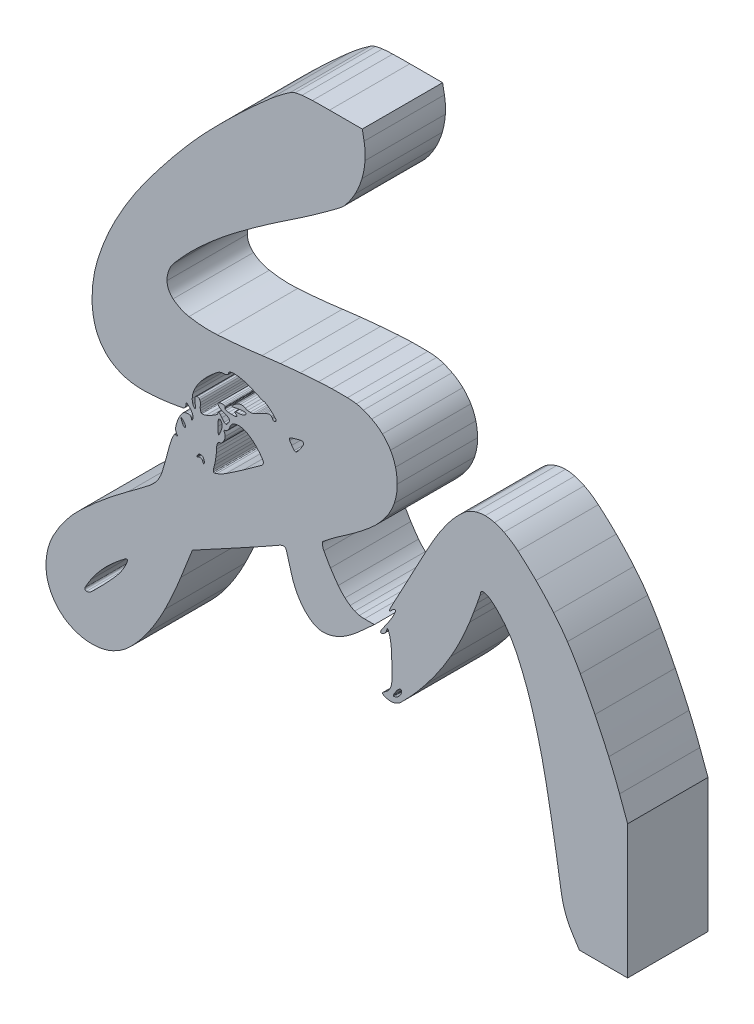
SolidWorks part; units mm, degrees
ref_plane "Front Plane" through (0, 0, 0) normal (0, 0, 1) x (1, 0, 0)
ref_plane "Top Plane" through (0, 0, 0) normal (0, 1, 0) x (1, 0, 0)
ref_plane "Right Plane" through (0, 0, 0) normal (1, 0, 0) x (0, 0, -1)
sketch "Sketch2" plane through (0, 0, 0) normal (0, 0, 1) x (1, 0, 0)
  line L0 (58.1325, 46.1079) -> (62.4633, 57.0965)
  line L1 (62.4633, 57.0965) -> (75.9817, 64.4271)
  line L2 (75.9817, 64.4271) -> (81.4318, 67.3962)
  line L3 (81.4318, 67.3962) -> (86.629, 70.2555)
  line L4 (86.629, 70.2555) -> (91.0276, 72.6996)
  line L5 (97.713, 74.0169) -> (98.2521, 72.1906)
  line L6 (98.2521, 72.1906) -> (98.8813, 70.0175)
  line L7 (98.8813, 70.0175) -> (99.54, 67.697)
  line L8 (125.4581, 62.5021) -> (130.4161, 67)
  line L9 (130.4161, 67) -> (126.7429, 67)
  line L10 (126.5831, 221.4085) -> (125.9094, 225)
  line L11 (125.9094, 225) -> (113.6772, 225)
  line L12 (84.7821, 120.3404) -> (86.2428, 119.6975)
  line L13 (87.5547, 119.1396) -> (88.6641, 118.6831)
  line L14 (89.9287, 114.9639) -> (89.0442, 114.5211)
  line L15 (89.0442, 114.5211) -> (87.9723, 113.9827)
  line L16 (87.9723, 113.9827) -> (86.8914, 113.4387)
  line L17 (86.8914, 113.4387) -> (85.977, 112.9771)
  line L18 (145.0185, 91.5) -> (143.1759, 88.0347)
  line L19 (143.1759, 88.0347) -> (141.1487, 84.2344)
  line L20 (141.1487, 84.2344) -> (139.2415, 80.6687)
  line L21 (139.2415, 80.6687) -> (137.8075, 78)
  line L22 (204.0561, 4.5726) -> (206.956, 0)
  line L23 (206.956, 0) -> (215.978, 0)
  line L24 (215.978, 0) -> (225, 0)
  line L25 (225, 0) -> (225, 24.9318)
  line L26 (225, 24.9318) -> (225, 49.8636)
  line L27 (225, 49.8636) -> (221.9881, 58.0323)
  arc A0 (98.9725, 223.3296) -> (91.3359, 217.4477) centre (142.3937, 159.0566) ccw
  arc A1 (91.3359, 217.4477) -> (80.6992, 207.7701) centre (331.2459, -56.9208) ccw
  arc A2 (80.6992, 207.7701) -> (69.7304, 196.9582) centre (342.3048, -68.6048) ccw
  arc A3 (69.7304, 196.9582) -> (60.5919, 187) centre (231.7944, 39.0629) ccw
  arc A4 (60.5919, 187) -> (44.8059, 167.1501) centre (295.9522, -16.3757) ccw
  arc A5 (44.8059, 167.1501) -> (33.7717, 149.478) centre (160.2656, 82.7777) ccw
  arc A6 (33.7717, 149.478) -> (27.1754, 133.6598) centre (117.9519, 105.0897) ccw
  arc A7 (27.1754, 133.6598) -> (25, 119.5018) centre (72.1599, 119.5018) ccw
  arc A8 (25, 119.5018) -> (25.9759, 112.0838) centre (53.6811, 119.5018) ccw
  arc A9 (25.9759, 112.0838) -> (28.8483, 106.1709) centre (42.735, 116.571) ccw
  arc A10 (28.8483, 106.1709) -> (33.4937, 102.0925) centre (40.8582, 115.1654) ccw
  arc A11 (33.4937, 102.0925) -> (39.6189, 99.9819) centre (42.3159, 117.7531) ccw
  arc A12 (39.6189, 99.9819) -> (45.2486, 99.6601) centre (44.1501, 129.8391) ccw
  arc A13 (45.2486, 99.6601) -> (52.2921, 100.2566) centre (42.5757, 173.0935) ccw
  arc A14 (52.2921, 100.2566) -> (58.8811, 101.3412) centre (37.8213, 208.7339) ccw
  arc A15 (58.8811, 101.3412) -> (60, 102.7008) centre (58.6145, 102.7008) ccw
  arc A16 (60.0652, 103.3967) -> (60, 102.7008) centre (63.7457, 102.7008) ccw
  arc A17 (60.2979, 103.573) -> (60.0652, 103.3967) centre (60.279, 103.3563) ccw
  arc A18 (60.7041, 103.3959) -> (60.2979, 103.573) centre (60.2373, 102.8798) ccw
  arc A19 (61.5804, 102.5625) -> (60.7041, 103.3959) centre (44.5195, 85.5017) ccw
  arc A20 (62.1476, 101.8659) -> (61.5804, 102.5625) centre (58.4608, 99.4429) ccw
  arc A21 (62.5492, 101.0818) -> (62.1476, 101.8659) centre (58.7353, 99.6233) ccw
  arc A22 (62.7365, 100.3314) -> (62.5492, 101.0818) centre (59.5482, 99.9342) ccw
  arc A23 (62.6593, 99.7411) -> (62.7365, 100.3314) centre (61.5607, 100.1849) ccw
  arc A24 (62.4218, 99.2055) -> (62.6593, 99.7411) centre (54.5524, 103.0164) ccw
  arc A25 (62.2615, 99.0881) -> (62.4218, 99.2055) centre (62.2309, 99.2979) ccw
  arc A26 (62.1376, 99.1775) -> (62.2615, 99.0881) centre (62.2457, 99.1967) ccw
  arc A27 (62.0789, 99.6564) -> (62.1376, 99.1775) centre (66.5589, 99.9622) ccw
  arc A28 (62.0789, 99.6564) -> (61.8949, 100.06) centre (61.4503, 99.6135) ccw
  arc A29 (61.8949, 100.06) -> (61.4536, 100.3275) centre (61.1237, 99.2854) ccw
  arc A30 (61.4536, 100.3275) -> (60.8046, 100.4144) centre (60.8806, 98.5175) ccw
  arc A31 (60.8046, 100.4144) -> (60.0427, 100.3009) centre (60.9479, 96.8397) ccw
  arc A32 (60.0427, 100.3009) -> (58.4846, 99.2035) centre (60.731, 97.6689) ccw
  arc A33 (58.4846, 99.2035) -> (57.0681, 96.5746) centre (70.239, 91.1736) ccw
  arc A34 (57.0681, 96.5746) -> (56.2329, 93.7146) centre (70.212, 91.1847) ccw
  arc A35 (56.2329, 93.7146) -> (56.5834, 91.865) centre (58.8188, 93.2466) ccw
  arc A36 (56.8204, 91.4259) -> (56.5834, 91.865) centre (52.9657, 89.6292) ccw
  arc A37 (56.815, 91.2024) -> (56.8204, 91.4259) centre (56.5923, 91.3196) ccw
  arc A38 (56.6544, 91.1412) -> (56.815, 91.2024) centre (56.7, 91.2629) ccw
  arc A39 (56.2953, 91.3175) -> (56.6544, 91.1412) centre (57.3783, 93.0697) ccw
  arc A40 (56.2953, 91.3175) -> (55.7849, 91.1994) centre (56.0997, 91.0009) ccw
  arc A41 (55.7849, 91.1994) -> (55.0801, 89.8876) centre (64.8532, 85.482) ccw
  arc A42 (55.0801, 89.8876) -> (54.3124, 87.8818) centre (71.9717, 82.273) ccw
  arc A43 (54.3124, 87.8818) -> (53.5476, 85.222) centre (102.2212, 72.6655) ccw
  arc A44 (51.1765, 76.7767) -> (53.5476, 85.222) centre (-146.3837, 136.7991) ccw
  arc A45 (49.3624, 73.0806) -> (51.1765, 76.7767) centre (38.9119, 80.5029) ccw
  arc A46 (46.4159, 70.003) -> (49.3624, 73.0806) centre (37.4294, 81.5559) ccw
  arc A47 (38.5117, 64.0517) -> (46.4159, 70.003) centre (-146.6931, 318.2601) ccw
  arc A48 (38.5117, 64.0517) -> (20.7518, 49.2864) centre (144.9076, -81.9855) ccw
  arc A49 (20.7518, 49.2864) -> (10.5895, 35.9714) centre (56.576, 11.4089) ccw
  arc A50 (10.5895, 35.9714) -> (7.8151, 24.1947) centre (31.4083, 24.8516) ccw
  arc A51 (7.8151, 24.1947) -> (11.7296, 13.9095) centre (24.5051, 24.6594) ccw
  arc A52 (11.7296, 13.9095) -> (16.0112, 10.3476) centre (23.8048, 24.0701) ccw
  arc A53 (16.0112, 10.3476) -> (21.4133, 8.3391) centre (24.9134, 26.022) ccw
  arc A54 (21.4133, 8.3391) -> (27.2661, 8.1176) centre (25.0366, 26.6446) ccw
  arc A55 (27.2661, 8.1176) -> (32.8489, 9.7292) centre (25.1044, 26.0814) ccw
  arc A56 (32.8489, 9.7292) -> (39.3723, 14.3529) centre (22.9802, 30.5665) ccw
  arc A57 (39.3723, 14.3529) -> (45.8866, 22.1873) centre (-2.6611, 55.9285) ccw
  arc A58 (45.8866, 22.1873) -> (52.2059, 32.8307) centre (-25.1859, 71.5834) ccw
  arc A59 (52.2059, 32.8307) -> (58.1325, 46.1079) centre (-94.2409, 106.1615) ccw
  arc A60 (91.0276, 72.6996) -> (93.2447, 73.9745) centre (41.8134, 160.8536) ccw
  arc A61 (95.1566, 75.0372) -> (93.2447, 73.9745) centre (113.7591, 39.321) ccw
  arc A62 (96.3011, 75.445) -> (95.1566, 75.0372) centre (97.1978, 71.1182) ccw
  arc A63 (97.0065, 75.3524) -> (96.3011, 75.445) centre (96.5207, 74.3851) ccw
  arc A64 (97.4483, 74.8456) -> (97.0065, 75.3524) centre (96.6081, 74.559) ccw
  arc A65 (97.713, 74.0169) -> (97.4483, 74.8456) centre (76.4663, 67.6891) ccw
  arc A66 (99.54, 67.697) -> (101.5193, 62.7234) centre (124.2446, 74.6478) ccw
  arc A67 (101.5193, 62.7234) -> (104.3859, 58.6357) centre (118.7877, 71.7844) ccw
  arc A68 (104.3859, 58.6357) -> (107.7326, 55.9243) centre (115.0327, 68.3561) ccw
  arc A69 (107.7326, 55.9243) -> (111.1322, 55) centre (111.1322, 61.7138) ccw
  arc A70 (111.1322, 55) -> (114.3727, 55.4474) centre (111.1322, 66.9579) ccw
  arc A71 (114.3727, 55.4474) -> (117.7122, 56.7752) centre (109.6818, 72.1098) ccw
  arc A72 (117.7122, 56.7752) -> (121.3361, 59.0778) centre (105.7891, 79.5433) ccw
  arc A73 (121.3361, 59.0778) -> (125.4581, 62.5021) centre (84.1117, 108.0785) ccw
  arc A74 (124.8181, 67.1788) -> (126.7429, 67) centre (126.7429, 77.4472) ccw
  arc A75 (123.0863, 67.71) -> (124.8181, 67.1788) centre (126.3071, 75.1224) ccw
  arc A76 (121.3674, 68.6716) -> (123.0863, 67.71) centre (127.0128, 76.7464) ccw
  arc A77 (119.4706, 70.16) -> (121.3674, 68.6716) centre (133.8896, 86.5824) ccw
  arc A78 (116.9314, 72.9113) -> (119.4706, 70.16) centre (131.2624, 83.5902) ccw
  arc A79 (114.0429, 77.1489) -> (116.9314, 72.9113) centre (165.7714, 109.3048) ccw
  arc A80 (111.5801, 81.443) -> (114.0429, 77.1489) centre (173.3859, 114.0381) ccw
  arc A81 (111, 83.7864) -> (111.5801, 81.443) centre (116.0236, 83.7864) ccw
  arc A82 (111.2406, 84.2918) -> (111, 83.7864) centre (111.651, 83.7864) ccw
  arc A83 (113.4645, 86.0629) -> (111.2406, 84.2918) centre (205.3287, -31.5713) ccw
  arc A84 (116.1742, 88.0924) -> (113.4645, 86.0629) centre (165.1493, 19.8795) ccw
  arc A85 (119.3898, 90.3383) -> (116.1742, 88.0924) centre (204.134, -34.4186) ccw
  arc A86 (119.3898, 90.3383) -> (128.5689, 97.2876) centre (56.3578, 183.1316) ccw
  arc A87 (128.5689, 97.2876) -> (134.5246, 103.6168) centre (104.4908, 125.9114) ccw
  arc A88 (134.5246, 103.6168) -> (137.8519, 109.922) centre (115.7444, 117.5577) ccw
  arc A89 (137.8519, 109.922) -> (138.9718, 116.7179) centre (118.5246, 116.5974) ccw
  arc A90 (138.9718, 116.7179) -> (138.3179, 121.8604) centre (117.4279, 116.591) ccw
  arc A91 (138.3179, 121.8604) -> (136.4575, 126.4089) centre (121.3825, 117.5886) ccw
  arc A92 (136.4575, 126.4089) -> (133.4568, 130.1619) centre (122.113, 118.016) ccw
  arc A93 (133.4568, 130.1619) -> (129.4599, 132.9749) centre (121.3319, 117.1797) ccw
  arc A94 (129.4599, 132.9749) -> (126.3756, 134.3466) centre (115.849, 106.5245) ccw
  arc A95 (126.3756, 134.3466) -> (123.7052, 135.055) centre (121.5939, 121.7084) ccw
  arc A96 (123.7052, 135.055) -> (120.3559, 135.3426) centre (120.0157, 111.7319) ccw
  arc A97 (120.3559, 135.3426) -> (114.5264, 135.3373) centre (117.6143, -54.9073) ccw
  arc A98 (114.5264, 135.3373) -> (109.5747, 135.1292) centre (116.0872, 39.181) ccw
  arc A99 (109.5747, 135.1292) -> (102.7453, 134.5966) centre (132.6587, -204.9678) ccw
  arc A100 (102.7453, 134.5966) -> (95.3604, 133.872) centre (135.5077, -237.305) ccw
  arc A101 (95.3604, 133.872) -> (88.5, 133.0445) centre (125.5632, -145.3621) ccw
  arc A102 (71.7969, 131.3896) -> (88.5, 133.0445) centre (55.5242, 380.749) ccw
  arc A103 (61.2042, 132.0029) -> (71.7969, 131.3896) centre (68.9811, 174.5386) ccw
  arc A104 (55.2638, 134.7535) -> (61.2042, 132.0029) centre (63.5578, 144.8757) ccw
  arc A105 (53, 139.5351) -> (55.2638, 134.7535) centre (59.1818, 139.5351) ccw
  arc A106 (55.4713, 146.3194) -> (53, 139.5351) centre (63.548, 139.5351) ccw
  arc A107 (65.0484, 156.4067) -> (55.4713, 146.3194) centre (143.0943, 72.7179) ccw
  arc A108 (79.262, 168.2983) -> (65.0484, 156.4067) centre (182.4811, 30.4836) ccw
  arc A109 (98.0934, 181.588) -> (79.262, 168.2983) centre (323.5476, -157.8641) ccw
  arc A110 (98.0934, 181.588) -> (105.4767, 186.5917) centre (-166.3038, 579.6742) ccw
  arc A111 (105.4767, 186.5917) -> (112.1241, 191.3089) centre (-84.2329, 460.9727) ccw
  arc A112 (112.1241, 191.3089) -> (117.5951, 195.37) centre (-106.3283, 491.3164) ccw
  arc A113 (117.5951, 195.37) -> (119.4848, 197.1643) centre (110.5471, 204.6849) ccw
  arc A114 (119.4848, 197.1643) -> (123.2583, 202.7225) centre (94.5057, 218.1829) ccw
  arc A115 (123.2583, 202.7225) -> (125.7969, 208.9144) centre (94.942, 217.9483) ccw
  arc A116 (125.7969, 208.9144) -> (126.9386, 215.2943) centre (96.8791, 217.3811) ccw
  arc A117 (126.9386, 215.2943) -> (126.5831, 221.4085) centre (102.8908, 216.9638) ccw
  arc A118 (113.6772, 225) -> (107.2821, 224.9286) centre (113.677, -61.3918) ccw
  arc A119 (107.2821, 224.9286) -> (103.4004, 224.6653) centre (108.2393, 182.0677) ccw
  arc A120 (103.4004, 224.6653) -> (100.8077, 224.1698) centre (105.3697, 207.3295) ccw
  arc A121 (100.8077, 224.1698) -> (98.9725, 223.3296) centre (102.4162, 218.2323) ccw
  arc A122 (86.2428, 119.6975) -> (87.5547, 119.1396) centre (125.0172, 209.0572) ccw
  arc A123 (88.6641, 118.6831) -> (89, 118.5831) centre (89.3488, 120.368) ccw
  arc A124 (90.4252, 117.9747) -> (89, 118.5831) centre (88.2888, 114.9434) ccw
  arc A125 (92.175, 116.5423) -> (90.4252, 117.9747) centre (81.3766, 105.1359) ccw
  arc A126 (93.6023, 115.0051) -> (92.175, 116.5423) centre (80.9796, 104.7166) ccw
  arc A127 (93.5528, 114.273) -> (93.6023, 115.0051) centre (93.1856, 114.6656) ccw
  arc A128 (93.2039, 114.0742) -> (93.5528, 114.273) centre (92.9611, 114.9056) ccw
  arc A129 (92.8414, 114.0837) -> (93.2039, 114.0742) centre (93.0374, 114.6443) ccw
  arc A130 (92.5203, 114.3089) -> (92.8414, 114.0837) centre (93.0795, 114.7645) ccw
  arc A131 (92.2918, 114.7139) -> (92.5203, 114.3089) centre (93.5856, 115.1769) ccw
  arc A132 (92.2918, 114.7139) -> (91.9742, 115.1974) centre (91.1349, 114.2999) ccw
  arc A133 (91.9742, 115.1974) -> (91.5037, 115.4124) centre (91.418, 114.6027) ccw
  arc A134 (91.5037, 115.4124) -> (90.8388, 115.3404) centre (91.3374, 113.8408) ccw
  arc A135 (90.8388, 115.3404) -> (89.9287, 114.9639) centre (93.0221, 108.7745) ccw
  arc A136 (85.01, 112.6087) -> (85.977, 112.9771) centre (83.729, 117.4232) ccw
  arc A137 (84.028, 112.4682) -> (85.01, 112.6087) centre (83.9262, 116.6822) ccw
  arc A138 (83.0801, 112.5626) -> (84.028, 112.4682) centre (83.9345, 116.3354) ccw
  arc A139 (82.2128, 112.8861) -> (83.0801, 112.5626) centre (83.8434, 115.9331) ccw
  arc A140 (82.2128, 112.8861) -> (81.3093, 113.2107) centre (80.6611, 109.9869) ccw
  arc A141 (81.3093, 113.2107) -> (80.413, 113.2282) centre (80.8127, 110.7407) ccw
  arc A142 (80.413, 113.2282) -> (79.4853, 112.923) centre (80.9038, 110.1738) ccw
  arc A143 (79.4853, 112.923) -> (78.4858, 112.2873) centre (82.5008, 107.0786) ccw
  arc A144 (78.4858, 112.2873) -> (77.2596, 111.3101) centre (108.0536, 73.9287) ccw
  arc A145 (77.2596, 111.3101) -> (77.2689, 111.0675) centre (77.3566, 111.1923) ccw
  arc A146 (77.2689, 111.0675) -> (77.6467, 110.9822) centre (77.5614, 111.4835) ccw
  arc A147 (77.6467, 110.9822) -> (79.7997, 111.3632) centre (49.9752, 273.588) ccw
  arc A148 (81.1568, 111.5606) -> (79.7997, 111.3632) centre (83.1181, 93.3134) ccw
  arc A149 (82.0584, 111.5459) -> (81.1568, 111.5606) centre (81.5483, 107.9178) ccw
  arc A150 (82.4598, 111.332) -> (82.0584, 111.5459) centre (81.966, 110.8891) ccw
  arc A151 (82.4907, 110.9849) -> (82.4598, 111.332) centre (82.2433, 111.1378) ccw
  arc A152 (82.1029, 110.6056) -> (82.4907, 110.9849) centre (81.5307, 111.5783) ccw
  arc A153 (81.4172, 110.2848) -> (82.1029, 110.6056) centre (80.065, 114.0695) ccw
  arc A154 (80.5743, 110.0634) -> (81.4172, 110.2848) centre (79.7146, 115.0504) ccw
  arc A155 (79.691, 109.9847) -> (80.5743, 110.0634) centre (79.6531, 115.4071) ccw
  arc A156 (79.691, 109.9847) -> (78.7122, 109.943) centre (79.7871, 96.2308) ccw
  arc A157 (78.7122, 109.943) -> (78.3331, 109.7772) centre (78.7615, 109.3137) ccw
  arc A158 (78.3331, 109.7772) -> (78.3273, 109.5241) centre (78.4527, 109.6478) ccw
  arc A159 (78.3273, 109.5241) -> (78.7893, 109.1514) centre (80.1947, 111.3664) ccw
  arc A160 (79.0766, 108.8137) -> (78.7893, 109.1514) centre (78.388, 108.5188) ccw
  arc A161 (78.9753, 108.544) -> (79.0766, 108.8137) centre (78.8852, 108.7317) ccw
  arc A162 (78.3339, 108.3753) -> (78.9753, 108.544) centre (78.216, 110.1274) ccw
  arc A163 (77.0833, 108.3333) -> (78.3339, 108.3753) centre (77.0833, 126.9683) ccw
  arc A164 (75.9699, 108.3923) -> (77.0833, 108.3333) centre (77.0833, 118.8687) ccw
  arc A165 (75.1192, 108.5781) -> (75.9699, 108.3923) centre (76.3925, 112.368) ccw
  arc A166 (74.6495, 108.8501) -> (75.1192, 108.5781) centre (75.5525, 109.8678) ccw
  arc A167 (74.603, 109.1667) -> (74.6495, 108.8501) centre (74.8144, 109.036) ccw
  arc A168 (74.603, 109.1667) -> (74.667, 109.4821) centre (74.2074, 109.4112) ccw
  arc A169 (74.667, 109.4821) -> (74.5088, 109.7552) centre (74.2379, 109.4159) ccw
  arc A170 (74.5088, 109.7552) -> (74.1197, 109.94) centre (73.92, 109.0176) ccw
  arc A171 (74.1197, 109.94) -> (73.559, 110) centre (73.559, 107.3498) ccw
  arc A172 (73.559, 110) -> (72.3614, 109.7153) centre (73.559, 107.3387) ccw
  arc A173 (72.3614, 109.7153) -> (72.0749, 109.0139) centre (72.621, 109.2001) ccw
  arc A174 (72.0749, 109.0139) -> (72.8162, 108.0965) centre (73.6978, 109.5671) ccw
  arc A175 (72.8162, 108.0965) -> (74.468, 107.3333) centre (77.1882, 115.3895) ccw
  arc A176 (75.6567, 106.8492) -> (74.468, 107.3333) centre (71.1061, 97.3771) ccw
  arc A177 (76.2077, 106.3595) -> (75.6567, 106.8492) centre (75.0765, 105.6415) ccw
  arc A178 (76.2969, 105.7728) -> (76.2077, 106.3595) centre (75.5861, 105.9649) ccw
  arc A179 (75.949, 105) -> (76.2969, 105.7728) centre (73.7124, 106.4716) ccw
  arc A180 (75.3545, 104.2593) -> (75.949, 105) centre (71.7378, 107.7708) ccw
  arc A181 (74.8752, 104.1049) -> (75.3545, 104.2593) centre (74.9696, 104.6331) ccw
  arc A182 (74.3444, 104.4) -> (74.8752, 104.1049) centre (75.0398, 105.026) ccw
  arc A183 (73.481, 105.4411) -> (74.3444, 104.4) centre (86.7357, 115.5539) ccw
  arc A184 (73.481, 105.4411) -> (72.9106, 106.1189) centre (66.1124, 99.8192) ccw
  arc A185 (72.9106, 106.1189) -> (72.435, 106.5093) centre (71.2476, 104.5778) ccw
  arc A186 (72.435, 106.5093) -> (72.1445, 106.5467) centre (72.2483, 106.2056) ccw
  arc A187 (72.1445, 106.5467) -> (72, 106.3516) centre (72.2039, 106.3516) ccw
  arc A188 (71.5632, 105.5006) -> (72, 106.3516) centre (70.9525, 106.3516) ccw
  arc A189 (69.6838, 104.3028) -> (71.5632, 105.5006) centre (59.7557, 121.9541) ccw
  arc A190 (67.5963, 103.3011) -> (69.6838, 104.3028) centre (60.94, 119.8487) ccw
  arc A191 (66.041, 103) -> (67.5963, 103.3011) centre (66.041, 107.1674) ccw
  arc A192 (65.7288, 103.1717) -> (66.041, 103) centre (66.041, 103.3697) ccw
  arc A193 (65.5054, 103.6854) -> (65.7288, 103.1717) centre (67.2612, 104.1435) ccw
  arc A194 (65.397, 104.4394) -> (65.5054, 103.6854) centre (68.792, 104.5429) ccw
  arc A195 (65.4322, 105.3333) -> (65.397, 104.4394) centre (71.7985, 104.6345) ccw
  arc A196 (65.4322, 105.3333) -> (65.4467, 106.2855) centre (60.3974, 105.886) ccw
  arc A197 (65.4467, 106.2855) -> (65.2528, 107.0272) centre (63.2741, 106.1136) ccw
  arc A198 (65.2528, 107.0272) -> (64.8745, 107.494) centre (64.1434, 106.515) ccw
  arc A199 (64.8745, 107.494) -> (64.3549, 107.6667) centre (64.3549, 106.7981) ccw
  arc A200 (64.3549, 107.6667) -> (63.8193, 107.4943) centre (64.3549, 106.7483) ccw
  arc A201 (63.8193, 107.4943) -> (63.4754, 107.0397) centre (64.3807, 106.7124) ccw
  arc A202 (63.4754, 107.0397) -> (63.354, 106.2766) centre (65.4077, 106.341) ccw
  arc A203 (63.354, 106.2766) -> (63.4667, 105.2106) centre (70.5968, 106.5036) ccw
  arc A204 (63.5939, 104.3092) -> (63.4667, 105.2106) centre (52.0312, 103.137) ccw
  arc A205 (63.5898, 103.6675) -> (63.5939, 104.3092) centre (60.6166, 104.0074) ccw
  arc A206 (63.4597, 103.4043) -> (63.5898, 103.6675) centre (63.1591, 103.7167) ccw
  arc A207 (63.2604, 103.4062) -> (63.4597, 103.4043) centre (63.361, 103.5069) ccw
  arc A208 (62.5878, 104.5678) -> (63.2604, 103.4062) centre (65.1027, 105.2485) ccw
  arc A209 (62.4059, 106.1797) -> (62.5878, 104.5678) centre (67.7601, 105.9677) ccw
  arc A210 (62.7227, 108.0691) -> (62.4059, 106.1797) centre (69.9896, 105.8795) ccw
  arc A211 (63.5232, 110.0449) -> (62.7227, 108.0691) centre (73.7963, 104.7325) ccw
  arc A212 (65.6306, 113.2542) -> (63.5232, 110.0449) centre (79.9842, 101.5326) ccw
  arc A213 (68.727, 116.5951) -> (65.6306, 113.2542) centre (93.8108, 90.2414) ccw
  arc A214 (71.9174, 119.3064) -> (68.727, 116.5951) centre (94.3695, 89.6543) ccw
  arc A215 (73.9823, 120) -> (71.9174, 119.3064) centre (73.9823, 116.5793) ccw
  arc A216 (73.9823, 120) -> (74.7545, 120.0737) centre (73.9823, 124.0841) ccw
  arc A217 (74.7545, 120.0737) -> (75.4073, 120.2938) centre (74.2705, 122.5874) ccw
  arc A218 (75.4073, 120.2938) -> (75.8473, 120.6181) centre (74.7104, 121.6999) ccw
  arc A219 (75.8473, 120.6181) -> (76, 121) centre (75.446, 121) ccw
  arc A220 (76.6849, 121.823) -> (76, 121) centre (76.837, 121) ccw
  arc A221 (78.839, 121.9392) -> (76.6849, 121.823) centre (78.2104, 113.5691) ccw
  arc A222 (81.7444, 121.4325) -> (78.839, 121.9392) centre (77.707, 106.8668) ccw
  arc A223 (84.7821, 120.3404) -> (81.7444, 121.4325) centre (75.9693, 100.5978) ccw
  arc A224 (103.869, 111.8438) -> (103.9682, 112.25) centre (102.9014, 112.2952) ccw
  arc A225 (103.5145, 111.1501) -> (103.869, 111.8438) centre (94.0543, 116.4231) ccw
  arc A226 (103.0326, 110.357) -> (103.5145, 111.1501) centre (92.6957, 117.1803) ccw
  arc A227 (102.4682, 109.5589) -> (103.0326, 110.357) centre (90.3071, 118.757) ccw
  arc A228 (101.4893, 108.3411) -> (102.4682, 109.5589) centre (81.3666, 125.5193) ccw
  arc A229 (101.0049, 108.1177) -> (101.4893, 108.3411) centre (101.0049, 108.7545) ccw
  arc A230 (100.5243, 108.3426) -> (101.0049, 108.1177) centre (101.0049, 108.7438) ccw
  arc A231 (99.5701, 109.5589) -> (100.5243, 108.3426) centre (120.0849, 124.6702) ccw
  arc A232 (98.8012, 110.7091) -> (99.5701, 109.5589) centre (111.7916, 118.5613) ccw
  arc A233 (98.7245, 111.2911) -> (98.8012, 110.7091) centre (99.4275, 111.0876) ccw
  arc A234 (99.1016, 111.7144) -> (98.7245, 111.2911) centre (99.3558, 111.1084) ccw
  arc A235 (100.3201, 112.1503) -> (99.1016, 111.7144) centre (103.7706, 100.5845) ccw
  arc A236 (102.3571, 112.7254) -> (100.3201, 112.1503) centre (120.8162, 43.4481) ccw
  arc A237 (103.3261, 112.8658) -> (102.3571, 112.7254) centre (103.4411, 108.6573) ccw
  arc A238 (103.7884, 112.6903) -> (103.3261, 112.8658) centre (103.3438, 112.2159) ccw
  arc A239 (103.9682, 112.25) -> (103.7884, 112.6903) centre (103.3985, 112.2742) ccw
  arc A240 (87.0997, 101.659) -> (85.9231, 102.9231) centre (68.8756, 85.8755) ccw
  arc A241 (88.0899, 100.4054) -> (87.0997, 101.659) centre (73.7399, 90.0884) ccw
  arc A242 (88.8105, 99.3062) -> (88.0899, 100.4054) centre (75.6842, 91.4863) ccw
  arc A243 (88.9786, 98.6731) -> (88.8105, 99.3062) centre (87.7843, 98.6948) ccw
  arc A244 (88.3498, 97.4668) -> (88.9786, 98.6731) centre (87.454, 98.7008) ccw
  arc A245 (81.5534, 92.6033) -> (88.3498, 97.4668) centre (-275.5146, 598.7614) ccw
  arc A246 (75.0593, 88.1799) -> (81.5534, 92.6033) centre (-56.414, 288.178) ccw
  arc A247 (71.5584, 86.384) -> (75.0593, 88.1799) centre (64.9934, 103.4921) ccw
  arc A248 (70.7131, 86.1697) -> (71.5584, 86.384) centre (70.2327, 89.8388) ccw
  arc A249 (70.3429, 86.3879) -> (70.7131, 86.1697) centre (70.6677, 86.516) ccw
  arc A250 (70.2899, 87.0305) -> (70.3429, 86.3879) centre (71.3803, 86.797) ccw
  arc A251 (70.6753, 88.6235) -> (70.2899, 87.0305) centre (100.6544, 80.5267) ccw
  arc A252 (70.6753, 88.6235) -> (70.9748, 89.9247) centre (53.5044, 93.2611) ccw
  arc A253 (70.9748, 89.9247) -> (71.231, 91.4628) centre (38.6075, 96.106) ccw
  arc A254 (71.231, 91.4628) -> (71.4114, 92.9895) centre (39.1938, 96.0226) ccw
  arc A255 (71.4114, 92.9895) -> (71.4761, 94.25) centre (56.6537, 94.3789) ccw
  arc A256 (71.5689, 95.303) -> (71.4761, 94.25) centre (78.1516, 94.192) ccw
  arc A257 (71.8287, 96.1922) -> (71.5689, 95.303) centre (75.4798, 94.6429) ccw
  arc A258 (72.2037, 96.7977) -> (71.8287, 96.1922) centre (73.9771, 95.2805) ccw
  arc A259 (72.643, 97) -> (72.2037, 96.7977) centre (72.643, 96.4219) ccw
  arc A260 (72.643, 97) -> (73.5798, 97.4013) centre (72.643, 98.294) ccw
  arc A261 (73.5798, 97.4013) -> (74.3537, 98.5619) centre (70.6509, 100.1925) ccw
  arc A262 (74.3537, 98.5619) -> (74.7122, 99.9713) centre (70.3189, 100.3387) ccw
  arc A263 (74.7122, 99.9713) -> (74.4442, 101.0902) centre (72.8815, 100.1244) ccw
  arc A264 (74.3044, 101.4377) -> (74.4442, 101.0902) centre (75.3801, 101.6687) ccw
  arc A265 (74.3384, 101.7328) -> (74.3044, 101.4377) centre (74.7575, 101.535) ccw
  arc A266 (74.5395, 101.9292) -> (74.3384, 101.7328) centre (74.703, 101.5607) ccw
  arc A267 (74.8736, 102) -> (74.5395, 101.9292) centre (74.8736, 101.1763) ccw
  arc A268 (74.8736, 102) -> (75.2993, 102.1427) centre (74.8736, 102.7064) ccw
  arc A269 (75.2993, 102.1427) -> (75.7604, 102.5875) centre (73.6949, 104.2672) ccw
  arc A270 (75.7604, 102.5875) -> (76.1839, 103.2347) centre (72.8514, 104.9531) ccw
  arc A271 (76.1839, 103.2347) -> (76.5, 104) centre (71.818, 105.486) ccw
  arc A272 (77.8668, 105.6032) -> (76.5, 104) centre (79.0865, 103.1791) ccw
  arc A273 (80.2064, 106.0197) -> (77.8668, 105.6032) centre (79.7346, 101.891) ccw
  arc A274 (83.1139, 105.068) -> (80.2064, 106.0197) centre (79.3429, 98.4643) ccw
  arc A275 (85.9231, 102.9231) -> (83.1139, 105.068) centre (76.5189, 93.5189) ccw
  arc A276 (72.4671, 99.4064) -> (73.0939, 100.9195) centre (12.1506, 125.279) ccw
  arc A277 (72.2602, 99.3666) -> (72.4671, 99.4064) centre (72.3501, 99.4565) ccw
  arc A278 (72.1166, 99.6996) -> (72.2602, 99.3666) centre (72.6074, 99.7138) ccw
  arc A279 (72.0634, 101.95) -> (72.1166, 99.6996) centre (285.8431, 105.8779) ccw
  arc A280 (72.0853, 103.4832) -> (72.0634, 101.95) centre (95.5137, 102.3809) ccw
  arc A281 (72.2654, 104.313) -> (72.0853, 103.4832) centre (74.6426, 103.3628) ccw
  arc A282 (72.5946, 104.5428) -> (72.2654, 104.313) centre (72.605, 104.1773) ccw
  arc A283 (73.0305, 104.3695) -> (72.5946, 104.5428) centre (72.6114, 103.9505) ccw
  arc A284 (73.4145, 103.7659) -> (73.0305, 104.3695) centre (71.8654, 103.2044) ccw
  arc A285 (73.5582, 102.9894) -> (73.4145, 103.7659) centre (71.1501, 102.9452) ccw
  arc A286 (73.4526, 102.0395) -> (73.5582, 102.9894) centre (69.8456, 102.9212) ccw
  arc A287 (73.0939, 100.9195) -> (73.4526, 102.0395) centre (65.3156, 104.0286) ccw
  arc A288 (59.5387, 95.4075) -> (59.8069, 95.4735) centre (59.6182, 95.6622) ccw
  arc A289 (59.2109, 95.6049) -> (59.5387, 95.4075) centre (59.779, 96.1772) ccw
  arc A290 (58.8663, 96.0593) -> (59.2109, 95.6049) centre (60.649, 97.0537) ccw
  arc A291 (58.5643, 96.7069) -> (58.8663, 96.0593) centre (63.1733, 98.4619) ccw
  arc A292 (58.2182, 97.6638) -> (58.5643, 96.7069) centre (86.8721, 107.4859) ccw
  arc A293 (58.2703, 97.8888) -> (58.2182, 97.6638) centre (58.4246, 97.7345) ccw
  arc A294 (58.4636, 97.8935) -> (58.2703, 97.8888) centre (58.3694, 97.7897) ccw
  arc A295 (59.1241, 97.2667) -> (58.4636, 97.8935) centre (44.8209, 82.8562) ccw
  arc A296 (59.5587, 96.7534) -> (59.1241, 97.2667) centre (56.3826, 94.5046) ccw
  arc A297 (59.8372, 96.2312) -> (59.5587, 96.7534) centre (57.6388, 95.3941) ccw
  arc A298 (59.9279, 95.7798) -> (59.8372, 96.2312) centre (58.5319, 95.7342) ccw
  arc A299 (59.8069, 95.4735) -> (59.9279, 95.7798) centre (59.5141, 95.7663) ccw
  arc A300 (66.8634, 87.1591) -> (66.9211, 87.691) centre (60.542, 88.1138) ccw
  arc A301 (66.7431, 87.0668) -> (66.8634, 87.1591) centre (66.7552, 87.1755) ccw
  arc A302 (66.5876, 87.1781) -> (66.7431, 87.0668) centre (66.7648, 87.2613) ccw
  arc A303 (66.3356, 87.7562) -> (66.5876, 87.1781) centre (76.8568, 91.998) ccw
  arc A304 (66.3356, 87.7562) -> (66.0607, 88.1851) centre (65.0643, 87.2437) ccw
  arc A305 (66.0607, 88.1851) -> (65.6639, 88.4494) centre (65.2882, 87.4552) ccw
  arc A306 (65.6639, 88.4494) -> (65.2068, 88.5064) centre (65.3174, 87.5325) ccw
  arc A307 (65.2068, 88.5064) -> (64.7601, 88.3517) centre (65.3289, 87.4314) ccw
  arc A308 (64.3605, 88.1458) -> (64.7601, 88.3517) centre (63.2368, 90.8165) ccw
  arc A309 (64.1866, 88.1974) -> (64.3605, 88.1458) centre (64.3051, 88.2776) ccw
  arc A310 (64.17, 88.4104) -> (64.1866, 88.1974) centre (64.3655, 88.3185) ccw
  arc A311 (64.4146, 88.8618) -> (64.17, 88.4104) centre (68.2457, 86.494) ccw
  arc A312 (65.1494, 89.4697) -> (64.4146, 88.8618) centre (65.6808, 88.0792) ccw
  arc A313 (66.0297, 89.438) -> (65.1494, 89.4697) centre (65.5522, 88.4158) ccw
  arc A314 (66.7177, 88.7548) -> (66.0297, 89.438) centre (65.4228, 88.1389) ccw
  arc A315 (66.9211, 87.691) -> (66.7177, 88.7548) centre (64.7797, 87.8329) ccw
  arc A316 (34.1069, 34.6229) -> (36.7566, 38.3121) centre (14.9516, 51.1773) ccw
  arc A317 (29.5013, 29.5861) -> (34.1069, 34.6229) centre (-58.0828, 114.2956) ccw
  arc A318 (24.6224, 24.6936) -> (29.5013, 29.5861) centre (-132.813, 186.5727) ccw
  arc A319 (22.9143, 24) -> (24.6224, 24.6936) centre (22.9143, 26.4499) ccw
  arc A320 (22.3481, 24.9396) -> (22.9143, 24) centre (22.9143, 24.6404) ccw
  arc A321 (24.639, 28.7491) -> (22.3481, 24.9396) centre (57.898, 6.1546) ccw
  arc A322 (28.0506, 33.2169) -> (24.639, 28.7491) centre (66.6191, 0.23) ccw
  arc A323 (31.8306, 37.1248) -> (28.0506, 33.2169) centre (61.818, 4.3363) ccw
  arc A324 (33.9373, 38.9927) -> (31.8306, 37.1248) centre (93.4724, -30.2749) ccw
  arc A325 (35.8555, 40.5679) -> (33.9373, 38.9927) centre (69.9678, -2.9279) ccw
  arc A326 (37.4962, 41.8183) -> (35.8555, 40.5679) centre (81.7699, -17.9767) ccw
  arc A327 (38.0469, 42) -> (37.4962, 41.8183) centre (38.0469, 41.0747) ccw
  arc A328 (38.2488, 41.7622) -> (38.0469, 42) centre (38.0469, 41.7954) ccw
  arc A329 (38.0332, 40.9167) -> (38.2488, 41.7622) centre (33.2867, 42.5772) ccw
  arc A330 (37.5288, 39.7274) -> (38.0332, 40.9167) centre (28.592, 44.2197) ccw
  arc A331 (36.7566, 38.3121) -> (37.5288, 39.7274) centre (16.1074, 50.4955) ccw
  arc A332 (165.3304, 121.0599) -> (163.8402, 119.9562) centre (170.7061, 112.2437) ccw
  arc A333 (163.8402, 119.9562) -> (161.9216, 118.1341) centre (191.1448, 89.2848) ccw
  arc A334 (161.9216, 118.1341) -> (159.9347, 115.9896) centre (194.773, 85.7031) ccw
  arc A335 (159.9347, 115.9896) -> (158.1769, 113.8136) centre (189.1518, 90.5898) ccw
  arc A336 (158.1769, 113.8136) -> (155.3719, 109.8764) centre (237.6825, 54.2034) ccw
  arc A337 (155.3719, 109.8764) -> (152.9881, 106.1058) centre (215.095, 69.4811) ccw
  arc A338 (152.9881, 106.1058) -> (150.0873, 100.9677) centre (287.8718, 26.5645) ccw
  arc A339 (150.0873, 100.9677) -> (145.0185, 91.5) centre (1467.6429, -610.5093) ccw
  arc A340 (137.8075, 78) -> (136.7572, 75.9914) centre (216.9713, 35.3261) ccw
  arc A341 (136.7572, 75.9914) -> (136.1363, 74.6297) centre (152.8939, 67.8108) ccw
  arc A342 (136.1363, 74.6297) -> (136.1192, 74.2829) centre (136.622, 74.432) ccw
  arc A343 (136.1192, 74.2829) -> (136.2816, 74.25) centre (136.2091, 74.3096) ccw
  arc A344 (137.8509, 75.6505) -> (136.2816, 74.25) centre (141.577, 69.8959) ccw
  arc A345 (138.3149, 75.286) -> (137.8509, 75.6505) centre (138.0204, 75.3887) ccw
  arc A346 (136.9069, 72.3284) -> (138.3149, 75.286) centre (124.0749, 80.2514) ccw
  arc A347 (134.1871, 68.2432) -> (136.9069, 72.3284) centre (75.9221, 109.9825) ccw
  arc A348 (134.1871, 68.2432) -> (133.1425, 66.7168) centre (169.1346, 43.2077) ccw
  arc A349 (133.1425, 66.7168) -> (132.7689, 65.8983) centre (135.6571, 65.0743) ccw
  arc A350 (132.7689, 65.8983) -> (132.9307, 65.5983) centre (133.0037, 65.8313) ccw
  arc A351 (132.9307, 65.5983) -> (133.4371, 65.6142) centre (133.1611, 66.3335) ccw
  arc A352 (133.4371, 65.6142) -> (134.0411, 65.966) centre (132.6559, 67.65) ccw
  arc A353 (134.0411, 65.966) -> (134.5661, 66.5204) centre (132.0837, 68.3455) ccw
  arc A354 (134.5661, 66.5204) -> (134.9366, 67.184) centre (132.1058, 68.3293) ccw
  arc A355 (134.9366, 67.184) -> (135.086, 67.857) centre (133.004, 67.9659) ccw
  arc A356 (135.2087, 68.1617) -> (135.086, 67.857) centre (135.5912, 67.8306) ccw
  arc A357 (135.4045, 68.1545) -> (135.2087, 68.1617) centre (135.3037, 68.0795) ccw
  arc A358 (135.704, 67.6011) -> (135.4045, 68.1545) centre (133.6446, 66.8443) ccw
  arc A359 (136.0496, 66.5627) -> (135.704, 67.6011) centre (119.084, 61.4934) ccw
  arc A360 (136.5333, 64.3942) -> (136.0496, 66.5627) centre (121.0209, 62.0721) ccw
  arc A361 (136.8031, 61.8102) -> (136.5333, 64.3942) centre (107.6937, 60.0771) ccw
  arc A362 (136.926, 58.0902) -> (136.8031, 61.8102) centre (66.5012, 57.6244) ccw
  arc A363 (136.9299, 51.777) -> (136.926, 58.0902) centre (-389.3394, 54.6098) ccw
  arc A364 (136.781, 50.5979) -> (136.9299, 51.777) centre (131.9758, 51.8037) ccw
  arc A365 (136.3533, 49.4273) -> (136.781, 50.5979) centre (130.9843, 52.0525) ccw
  arc A366 (135.7073, 48.4013) -> (136.3533, 49.4273) centre (131.2588, 51.9183) ccw
  arc A367 (134.9126, 47.6513) -> (135.7073, 48.4013) centre (132.7491, 50.74) ccw
  arc A368 (134.9126, 47.6513) -> (133.7558, 46.7961) centre (151.0273, 24.6443) ccw
  arc A369 (133.7558, 46.7961) -> (133.506, 46.3707) centre (134.1671, 46.2686) ccw
  arc A370 (133.506, 46.3707) -> (133.6817, 46.0192) centre (133.8417, 46.3188) ccw
  arc A371 (133.6817, 46.0192) -> (134.5958, 45.6016) centre (137.4979, 53.1643) ccw
  arc A372 (134.5958, 45.6016) -> (140.287, 46.7841) centre (136.5216, 50.62) ccw
  arc A373 (140.287, 46.7841) -> (149.6229, 57.2094) centre (64.0564, 124.4417) ccw
  arc A374 (149.6229, 57.2094) -> (158.9466, 70.9639) centre (56.5756, 130.3198) ccw
  arc A375 (158.9466, 70.9639) -> (165.9619, 85.5211) centre (67.331, 124.0839) ccw
  arc A376 (165.9619, 85.5211) -> (167.5092, 89.5566) centre (-140.183, 205.2175) ccw
  arc A377 (167.5092, 89.5566) -> (168.8138, 93.1313) centre (-17.7851, 159.208) ccw
  arc A378 (168.8138, 93.1313) -> (169.8748, 96.1744) centre (-144.5044, 204.0804) ccw
  arc A379 (169.8748, 96.1744) -> (170, 96.9246) centre (167.689, 96.9246) ccw
  arc A380 (170.6065, 97.7989) -> (170, 96.9246) centre (170.9333, 96.9246) ccw
  arc A381 (171.9385, 97.7947) -> (170.6065, 97.7989) centre (171.267, 96.0319) ccw
  arc A382 (174.0335, 96.6151) -> (171.9385, 97.7947) centre (169.0537, 90.2213) ccw
  arc A383 (176.4752, 94.4582) -> (174.0335, 96.6151) centre (157.8379, 75.8209) ccw
  arc A384 (183.4425, 84.561) -> (176.4752, 94.4582) centre (151.4744, 69.4574) ccw
  arc A385 (189.2569, 69.4439) -> (183.4425, 84.561) centre (84.658, 37.8894) ccw
  arc A386 (194.5919, 47.7814) -> (189.2569, 69.4439) centre (-18.1367, 6.8792) ccw
  arc A387 (200.0464, 16.3226) -> (194.5919, 47.7814) centre (-663.3616, -117.1796) ccw
  arc A388 (200.0464, 16.3226) -> (200.7127, 12.8989) centre (244.4853, 23.1938) ccw
  arc A389 (200.7127, 12.8989) -> (201.6043, 9.7973) centre (232.8274, 20.452) ccw
  arc A390 (201.6043, 9.7973) -> (202.7191, 7.0204) centre (228.3829, 18.9355) ccw
  arc A391 (202.7191, 7.0204) -> (204.0561, 4.5726) centre (222.116, 16.0259) ccw
  arc A392 (221.9881, 58.0323) -> (217.9436, 68.0348) centre (58.7039, -2.1726) ccw
  arc A393 (217.9436, 68.0348) -> (212.7809, 79.0954) centre (-42.3331, -46.7193) ccw
  arc A394 (212.7809, 79.0954) -> (207.3474, 89.5362) centre (-30.8577, -41.0599) ccw
  arc A395 (207.3474, 89.5362) -> (202.5096, 97.5287) centre (111.6277, 37.0579) ccw
  arc A396 (202.5096, 97.5287) -> (197.3792, 104.3174) centre (143.4825, 58.2534) ccw
  arc A397 (197.3792, 104.3174) -> (190.7721, 111.4432) centre (106.0395, 26.2517) ccw
  arc A398 (190.7721, 111.4432) -> (184.0627, 117.6024) centre (110.5154, 30.7519) ccw
  arc A399 (184.0627, 117.6024) -> (178.8176, 121.0931) centre (166.3903, 96.7335) ccw
  arc A400 (178.8176, 121.0931) -> (175.2755, 122.4539) centre (170.5871, 104.9599) ccw
  arc A401 (175.2755, 122.4539) -> (171.7955, 122.9077) centre (171.8282, 109.5911) ccw
  arc A402 (171.7955, 122.9077) -> (168.457, 122.433) centre (171.8254, 110.722) ccw
  arc A403 (168.457, 122.433) -> (165.3304, 121.0599) centre (171.9964, 110.1275) ccw
  arc A404 (140.0791, 48.993) -> (140.3913, 49.5773) centre (137.8979, 50.5341) ccw
  arc A405 (139.5921, 48.4138) -> (140.0791, 48.993) centre (136.396, 51.5953) ccw
  arc A406 (139.0164, 47.9254) -> (139.5921, 48.4138) centre (136.4078, 51.5835) ccw
  arc A407 (138.4373, 47.6143) -> (139.0164, 47.9254) centre (137.5042, 50.0461) ccw
  arc A408 (137.7397, 47.4055) -> (138.4373, 47.6143) centre (136.7105, 52.1144) ccw
  arc A409 (137.5321, 47.5519) -> (137.7397, 47.4055) centre (137.7029, 47.5738) ccw
  arc A410 (137.613, 47.9609) -> (137.5321, 47.5519) centre (138.1844, 47.6354) ccw
  arc A411 (138.2552, 49.037) -> (137.613, 47.9609) centre (164.5768, 32.5989) ccw
  arc A412 (139.2663, 50.4009) -> (138.2552, 49.037) centre (147.2995, 43.3887) ccw
  arc A413 (140.1571, 50.9476) -> (139.2663, 50.4009) centre (140.587, 49.248) ccw
  arc A414 (140.5728, 50.6325) -> (140.1571, 50.9476) centre (140.239, 50.6239) ccw
  arc A415 (140.3913, 49.5773) -> (140.5728, 50.6325) centre (137.826, 50.5617) ccw
  arc A416 (74, 118) -> (74.1156, 117.6186) centre (74.687, 118) ccw
  arc A417 (74.1156, 117.6186) -> (74.4406, 117.2938) centre (75.0914, 118.2699) ccw
  arc A418 (74.4406, 117.2938) -> (74.9265, 117.0747) centre (75.3435, 118.648) ccw
  arc A419 (74.9265, 117.0747) -> (76.0735, 117.0747) centre (75.5, 119.2387) ccw
  arc A420 (76.0735, 117.0747) -> (76.5594, 117.2938) centre (75.6565, 118.648) ccw
  arc A421 (76.5594, 117.2938) -> (76.8844, 117.6186) centre (75.9086, 118.2699) ccw
  arc A422 (76.8844, 117.6186) -> (76.8844, 118.3814) centre (76.313, 118) ccw
  arc A423 (76.8844, 118.3814) -> (76.5594, 118.7062) centre (75.9086, 117.7301) ccw
  arc A424 (76.5594, 118.7062) -> (76.0735, 118.9253) centre (75.6565, 117.352) ccw
  arc A425 (76.0735, 118.9253) -> (74.9265, 118.9253) centre (75.5, 116.7613) ccw
  arc A426 (74.9265, 118.9253) -> (74.4406, 118.7062) centre (75.3435, 117.352) ccw
  arc A427 (74.4406, 118.7062) -> (74.1156, 118.3814) centre (75.0914, 117.7301) ccw
  arc A428 (74.1156, 118.3814) -> (74, 118) centre (74.687, 118) ccw
  arc A429 (85.8125, 116.3169) -> (86.3594, 116.1609) centre (86.8428, 118.8916) ccw
  arc A430 (86.3594, 116.1609) -> (86.9169, 116.1234) centre (86.8104, 118.7087) ccw
  arc A431 (86.9169, 116.1234) -> (87.4022, 116.2026) centre (86.8328, 118.1663) ccw
  arc A432 (87.4022, 116.2026) -> (87.7292, 116.3958) centre (87.1898, 116.9352) ccw
  arc A433 (87.7292, 116.3958) -> (87.7754, 116.6147) centre (87.5843, 116.5407) ccw
  arc A434 (87.7754, 116.6147) -> (87.5928, 116.7993) centre (87.472, 116.4973) ccw
  arc A435 (87.5928, 116.7993) -> (87.1128, 116.9101) centre (86.9961, 115.3081) ccw
  arc A436 (87.1128, 116.9101) -> (86.4167, 116.9211) centre (86.6683, 110.8113) ccw
  arc A437 (86.4167, 116.9211) -> (85.6703, 116.862) centre (86.8245, 107.0199) ccw
  arc A438 (85.6703, 116.862) -> (85.3786, 116.7207) centre (85.7279, 116.3714) ccw
  arc A439 (85.3786, 116.7207) -> (85.3958, 116.5384) centre (85.4626, 116.6367) ccw
  arc A440 (85.3958, 116.5384) -> (85.8125, 116.3169) centre (86.6255, 118.3485) ccw
  arc A441 (68.6243, 113.6817) -> (66.9066, 112.8975) centre (83.6572, 78.4802) ccw
  arc A442 (66.9066, 112.8975) -> (66.4521, 112.4228) centre (67.3213, 112.0456) ccw
  arc A443 (66.4521, 112.4228) -> (66.5413, 111.9028) centre (66.8942, 112.2309) ccw
  arc A444 (66.5413, 111.9028) -> (67.471, 111.024) centre (73.8117, 118.6641) ccw
  arc A445 (67.471, 111.024) -> (68.4702, 110.2789) centre (75.1331, 120.2563) ccw
  arc A446 (68.4702, 110.2789) -> (69.0615, 110.132) centre (68.97, 111.0274) ccw
  arc A447 (69.0615, 110.132) -> (69.556, 110.4062) centre (68.9885, 110.8468) ccw
  arc A448 (69.556, 110.4062) -> (70.1465, 111.2972) centre (63.9237, 114.7797) ccw
  arc A449 (70.6187, 111.9485) -> (70.1465, 111.2972) centre (73.15, 109.6164) ccw
  arc A450 (71.2455, 112.4998) -> (70.6187, 111.9485) centre (73.5489, 109.2489) ccw
  arc A451 (71.9246, 112.8753) -> (71.2455, 112.4998) centre (73.2645, 109.6503) ccw
  arc A452 (72.5497, 113) -> (71.9246, 112.8753) centre (72.5497, 111.3707) ccw
  arc A453 (72.5497, 113) -> (73.1041, 113.0748) centre (72.5497, 115.0911) ccw
  arc A454 (73.1041, 113.0748) -> (73.574, 113.2938) centre (72.6923, 114.5725) ccw
  arc A455 (73.574, 113.2938) -> (73.8882, 113.6187) centre (72.9232, 114.2376) ccw
  arc A456 (73.8882, 113.6187) -> (74, 114) centre (73.2936, 114) ccw
  arc A457 (74, 114) -> (73.609, 114.6747) centre (73.2224, 114) ccw
  arc A458 (73.609, 114.6747) -> (72.6457, 114.9009) centre (72.748, 113.1721) ccw
  arc A459 (72.6457, 114.9009) -> (70.9958, 114.5823) centre (73.0242, 108.5081) ccw
  arc A460 (70.9958, 114.5823) -> (68.6243, 113.6817) centre (80.8787, 84.9864) ccw
extrude "Boss-Extrude1" add sketch "Sketch2" along normal blind 30 contours A120 A121 A0 A1 A2 A3 A4 A5 A6 A7 A8 A9 A10 A11 A12 A13 A14 A15 A16 A17 A18 A19 A20 A21 A22 A23 A24 A25 A26 A27 A28 A29 A30 A31 A32 A33 A34 A35 A36 A37 A38 A39 A40 A41 A42 A43 A44 A45 A46 A47 A48 | A402 A403 A332 A333 A334 A335 A336 A337 A338 A339 L18 L19 L20 L21 A340 A341 A342 A343 A344 A345 A346 A347 A348 A349 A350 A351 A352 A353 A354 A355 A356 A357 A358 A359 A360 A361 A362 A363 A364 A365 A366 A367 A368 A369 A370 A371 A372 A373 A374 A375 A376 region at (53.0011, 40.4371, 0) region at (148.8992, 95.5131, 0)
scale "Scale2" bodies to scale 101 102 scale about origin uniform scaling yes scale factor 5
